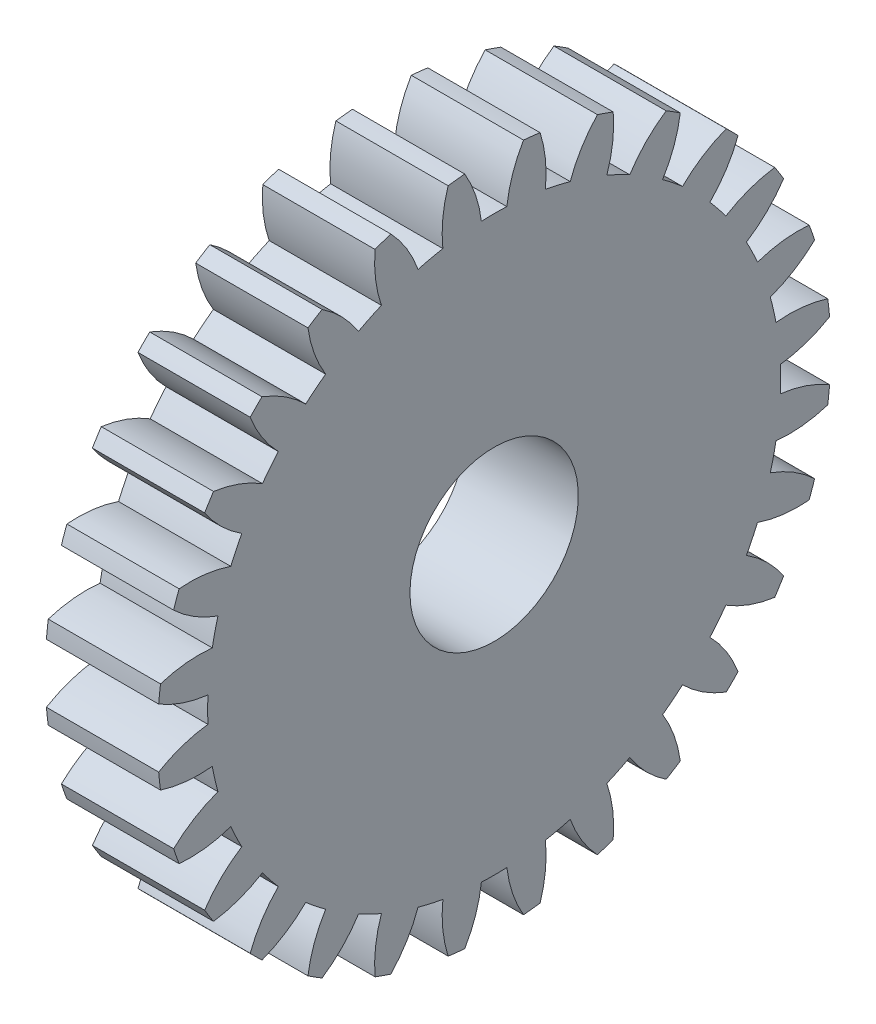
SolidWorks part; units mm, degrees
ref_plane "Plane1" through (0, 0, 0) normal (0, 0, 1) x (1, 0, 0)
ref_plane "Plane2" through (0, 0, 0) normal (0, 1, 0) x (1, 0, 0)
ref_plane "Plane3" through (0, 0, 0) normal (1, 0, 0) x (0, 0, -1)
sketch "HoldingSke" plane through (0, 0, 0) normal (0, 1, 0) x (1, 0, 0)
  line L0 (0, 0) -> (448.5374, -238.4916)
  line L1 (-15, 0) -> (100, 0) construction
  line L2 (0, 0) -> (-2.1039, 2.3779)
  line L3 (0, 0) -> (-11.863, 4.5341)
  line L4 (0, 0) -> (7.6251, 4.0544)
  line L5 (0, 0) -> (-47.5972, -17.7524)
  line L6 (0, 0) -> (-5.2639, -3.5516)
  line L7 (-2.1039, 2.3779) -> (8.8308, 51.9871)
  line L8 (-76.2, 54.61) -> (-65.4837, 54.61)
  line L9 (-67.7845, 28.3722) -> (-49.3413, 33.142)
  line L10 (-76.2, 71.12) -> (104.1128, 71.12)
  line L11 (0, 0) -> (-6.35, 0)
  line L12 (-76.2, 101.6) -> (-76.1492, 101.6)
  line L13 (24.9733, 27.94) -> (52.9518, 28.4284)
  line L14 (24.9733, 27.94) -> (25.0241, 27.9398)
  line L15 (24.9733, 27.94) -> (100.4021, 29.52)
  circle A0 centre (0, 0) radius 4.7625
  circle A1 centre (0, 0) radius 16.2052
  circle A2 centre (0, 0) radius 38.1
  circle A3 centre (0, 0) radius 4.7625
  dimension "Num_teeth" = 28
  dimension "H" = 19.05
  dimension "Pitch_radius" = 180.3128
  dimension "Width" = 6.35
  dimension "Thickness" = 6.35
sketch "BasProSke" plane through (0, 0, 0) normal (0, 1, 0) x (1, 0, 0)
  line L0 (-10, 0) -> (60, 0) construction
  line L1 (0, 0) -> (0, 19.05)
  line L2 (0, 0) -> (6.35, 0)
  line L3 (6.35, 0) -> (6.35, 19.05)
  line L4 (6.35, 19.05) -> (0, 19.05)
  dimension "Thickness" = 6.35
  dimension "Diameter" = 38.1
revolve "Base-Revolve" add sketch "BasProSke" angle 360 about L0
sketch "TooCutSke" plane through (0, 0, 0) normal (1, 0, 0) x (0, 0, -1)
  line L1 (0, 0) -> (0, 107) construction
  line L2 (0, 0) -> (-1.0858, 17.7468) construction
  line L3 (0, 0) -> (-3.9763, 35.2903) construction
  line L4 (-1.0858, 17.7468) -> (-1.9881, 17.6451) construction
  arc A0 (0.7203, 16.1892) -> (-0.7203, 16.1892) centre (0, 0) ccw
  arc A1 (1.6778, 19.0015) -> (-1.6778, 19.0015) centre (0, 0) ccw
  circle A2 centre (0, 0) radius 17.78 construction
  circle A3 centre (0, 0) radius 17.2137 construction
  arc A4 (-0.7203, 16.1892) -> (-1.6778, 19.0015) centre (-7.7831, 15.3536) ccw
  arc A5 (1.6778, 19.0015) -> (0.7203, 16.1892) centre (7.7831, 15.3536) ccw
extrude "ToothCut" cut sketch "TooCutSke" along normal through all
fillet "Breaks" [suppressed] radius 0.0254 tangent propagation no
fillet "RootFillets" [suppressed] radius 0.3048
pattern_circular "TeethCuts" count 28 every 12.857 about axis through (-10, 0, 0) along (1, 0, 0) of "ToothCut", "RootFillets", "Breaks"
sketch "HubNeaOneSke" plane through (0, 0, 0) normal (-1, 0, 0) x (0, 0, 1)
  circle A0 centre (0, 0) radius 16.2052
  dimension "Diameter" = 32.4104
extrude "HubNearOne" [suppressed] add sketch "HubNeaOneSke" along normal blind 44.4501
sketch "HubNeaBotSke" plane through (0, 0, 0) normal (-1, 0, 0) x (0, 0, 1)
  circle A0 centre (0, 0) radius 16.2052
  dimension "Diameter" = 32.4104
extrude "HubNearBoth" [suppressed] add sketch "HubNeaBotSke" along normal blind 22.225
ref_plane "FarPln" through (6.35, 0, 0) normal (1, 0, 0) x (0, 0, -1)
sketch "HubFarSke" plane through (6.35, 0, 0) normal (1, 0, 0) x (0, 0, -1)
  circle A0 centre (0, 0) radius 16.2052
  dimension "Diameter" = 32.4104
extrude "HubFar" [suppressed] add sketch "HubFarSke" along normal blind 22.225
sketch "BorSke" plane through (0, 0, 0) normal (1, 0, 0) x (0, 0, -1)
  circle A0 centre (0, 0) radius 4.7625
  dimension "Diameter" = 9.525
extrude "Bore" cut sketch "BorSke" along normal mid plane 101.6001
sketch "KeySke" plane through (0, 0, 0) normal (1, 0, 0) x (0, 0, -1)
  line L0 (-1.1913, 0) -> (-1.1913, 5.9538)
  line L1 (-1.1913, 5.9538) -> (1.1913, 5.9538)
  line L2 (1.1913, 5.9538) -> (1.1913, 0)
  line L3 (0, 0) -> (0, 34) construction
  line L4 (-1.1913, 0) -> (1.1913, 0)
  dimension "Width" = 2.3825
extrude "Keyway" [suppressed] cut sketch "KeySke" along normal mid plane 101.6001
pattern_circular "Keyway2" [suppressed] count 2 every 90 about axis through (-10, 0, 0) along (1, 0, 0) reverse direction yes
equation "' \"Pitch@HoldingSke\" = 4"
equation "' \"Num_teeth@HoldingSke\" = 12"
equation "' \"Ap@HoldingSke\" =  20"
equation "' \"Ap@HoldingSke\" = 20"
equation "' \"Width@HoldingSke\" = 0.5"
equation "' \"Hub_dia@HoldingSke\"= 1"
equation "' \"Hub_dia@HoldingSke\" = 1"
equation "' \"Overall_len@HoldingSke\" = 1.0"
equation "' \"Bore@HoldingSke\" = 0.75"
equation "' \"T_dim@HoldingSke\" = 0.85"
equation "' \"Width@KeySke\" = 0.25"
equation "' \"Show_teeth@HoldingSke\" = 13"
equation "' \"Backlash@HoldingSke\" = 0.009"
equation "' \"Addendum_fac@HoldingSke\" = 1.0"
equation "' \"Dedendum_fac@HoldingSke\" = 1.25"
equation "' \"Dedendum_add@HoldingSke\" = 0.00005"
equation "' \"Clearance_fac@HoldingSke\" = 0.25"
equation "' \"Pitch@HoldingSke\" = 0.5"
equation "' \"Num_teeth@HoldingSke\" = 23"
equation "' \"Show_teeth@HoldingSke\" = 23"
equation "' \"Backlash@HoldingSke\" = 0.0375"
equation "\"Overcut_dia@TooCutSke\" = (\"Num_teeth@HoldingSke\" + 2 * \"Addendum_fac@HoldingSke\") / \"Pitch@HoldingSke\" + 0.002"
equation "\"Pitch_dia@TooCutSke\" = \"Num_teeth@HoldingSke\" / \"Pitch@HoldingSke\""
equation "\"Base_dia@TooCutSke\" = \"Num_teeth@HoldingSke\" / \"Pitch@HoldingSke\" * cos((\"Ap@HoldingSke\"  * 3.14159265 / 180))"
equation "\"Root_dia@TooCutSke\" = (\"Num_teeth@HoldingSke\" + 2) / \"Pitch@HoldingSke\" - 2 * (\"Addendum_fac@HoldingSke\" + \"Dedendum_fac@HoldingSke\") / \"Pitch@HoldingSke\" - \"Dedendum_add@HoldingSke\" * 2"
equation "\"Half_ang@TooCutSke\" = 180 / \"Num_teeth@HoldingSke\""
equation "\"Half_CT@TooCutSke\" = \"Num_teeth@HoldingSke\" / \"Pitch@HoldingSke\" * sin((3.14159265 / 2 / \"Num_teeth@HoldingSke\")) / 2 - 7 * \"Backlash@HoldingSke\" / 4"
equation "\"Flank_rad@TooCutSke\" = \"Num_teeth@HoldingSke\" / \"Pitch@HoldingSke\" / 5"
equation "\"Radius@RootFillets\" = \"Clearance_fac@HoldingSke\" / \"Pitch@HoldingSke\" + \"Dedendum_add@HoldingSke\""
equation "\"Break_rad@Breaks\" = 0.02 / \"Pitch@HoldingSke\""
equation "\"Thickness@HoldingSke\" = \"Width@HoldingSke\""
equation "\"OAL@HoldingSke\" = \"Thickness@HoldingSke\""
equation "\"MHD@HoldingSke\" = (\"Num_teeth@HoldingSke\" + 2) / \"Pitch@HoldingSke\" - 2 * (\"Addendum_fac@HoldingSke\" + \"Dedendum_fac@HoldingSke\")  / \"Pitch@HoldingSke\" - \"Dedendum_add@HoldingSke\" * 2"
equation "\"MBD@HoldingSke\" = (\"Num_teeth@HoldingSke\" + 2) / \"Pitch@HoldingSke\" - 2 * (\"Addendum_fac@HoldingSke\" + \"Dedendum_fac@HoldingSke\")  / \"Pitch@HoldingSke\" - \"Dedendum_add@HoldingSke\" * 2 - 0.002"
equation "\"MHD@HoldingSke\" = ((sgn( \"MHD@HoldingSke\" - \"Hub_dia@HoldingSke\" )-1)*( \"MHD@HoldingSke\" - \"Hub_dia@HoldingSke\" ))/-2+ \"Hub_dia@HoldingSke\""
equation "\"MBD@HoldingSke\" = ((sgn( \"MBD@HoldingSke\" - \"Bore@HoldingSke\" )-1)*( \"MBD@HoldingSke\" - \"Bore@HoldingSke\" ))/-2+ \"Bore@HoldingSke\""
equation "\"OAL@HoldingSke\" = ((sgn( \"OAL@HoldingSke\" - \"Overall_len@HoldingSke\" )+1)*( \"OAL@HoldingSke\" - \"Overall_len@HoldingSke\" ))/2 + \"Overall_len@HoldingSke\" + 0.000002"
equation "\"Num_teeth@TeethCuts\" = int( \"Show_teeth@HoldingSke\" ) + 1"
equation "\"Num_teeth@TeethCuts\" = ((sgn( \"Num_teeth@TeethCuts\" - \"Num_teeth@HoldingSke\" )-1)*( \"Num_teeth@TeethCuts\" - \"Num_teeth@HoldingSke\" ))/-2+ \"Num_teeth@HoldingSke\""
equation "\"Num_teeth@TeethCuts\" = ((sgn( \"Num_teeth@TeethCuts\" - 2.0)+1)*( \"Num_teeth@TeethCuts\" - 2.0))/2 +2.0"
equation "\"Angle@TeethCuts\" = 360.0 / \"Num_teeth@HoldingSke\""
equation "\"Diameter@BasProSke\" = (\"Num_teeth@HoldingSke\" + 2 * \"Addendum_fac@HoldingSke\") / \"Pitch@HoldingSke\""
equation "\"Thickness@BasProSke\"  = \"Thickness@HoldingSke\""
equation "' \"Fillet_rad@BasProSke\" =  \"Thickness@HoldingSke\" * 0.05"
equation "' \"Fillet_rad@BasProSke\" = \"Thickness@HoldingSke\" * 0.05"
equation "\"MHD@HoldingSke\" = ((sgn( \"MHD@HoldingSke\" - \"Root_dia@TooCutSke\" )-1)*( \"MHD@HoldingSke\" - \"Root_dia@TooCutSke\" ))/-2+ \"Root_dia@TooCutSke\""
equation "\"Diameter@HubNeaOneSke\" = \"MHD@HoldingSke\""
equation "\"Length@HubNearOne\" = \"OAL@HoldingSke\" - \"Thickness@BasProSke\""
equation "\"Diameter@HubNeaBotSke\" = \"MHD@HoldingSke\""
equation "\"Length@HubNearBoth\" = ( \"OAL@HoldingSke\" - \"Thickness@BasProSke\" ) / 2.0"
equation "\"Thickness@FarPln\" = \"Thickness@BasProSke\""
equation "\"Diameter@HubFarSke\" = \"MHD@HoldingSke\""
equation "\"Length@HubFar\" = ( \"OAL@HoldingSke\" - \"Thickness@BasProSke\" ) / 2.0"
equation "\"Diameter@BorSke\" = \"MBD@HoldingSke\""
equation "\"D1@Bore\" = \"OAL@HoldingSke\" * 2.0"
equation "\"D1@Keyway\" = \"OAL@HoldingSke\" * 2.0"
equation "\"Offset@KeySke\" = \"T_dim@HoldingSke\" - \"MBD@HoldingSke\" / 2.0"
